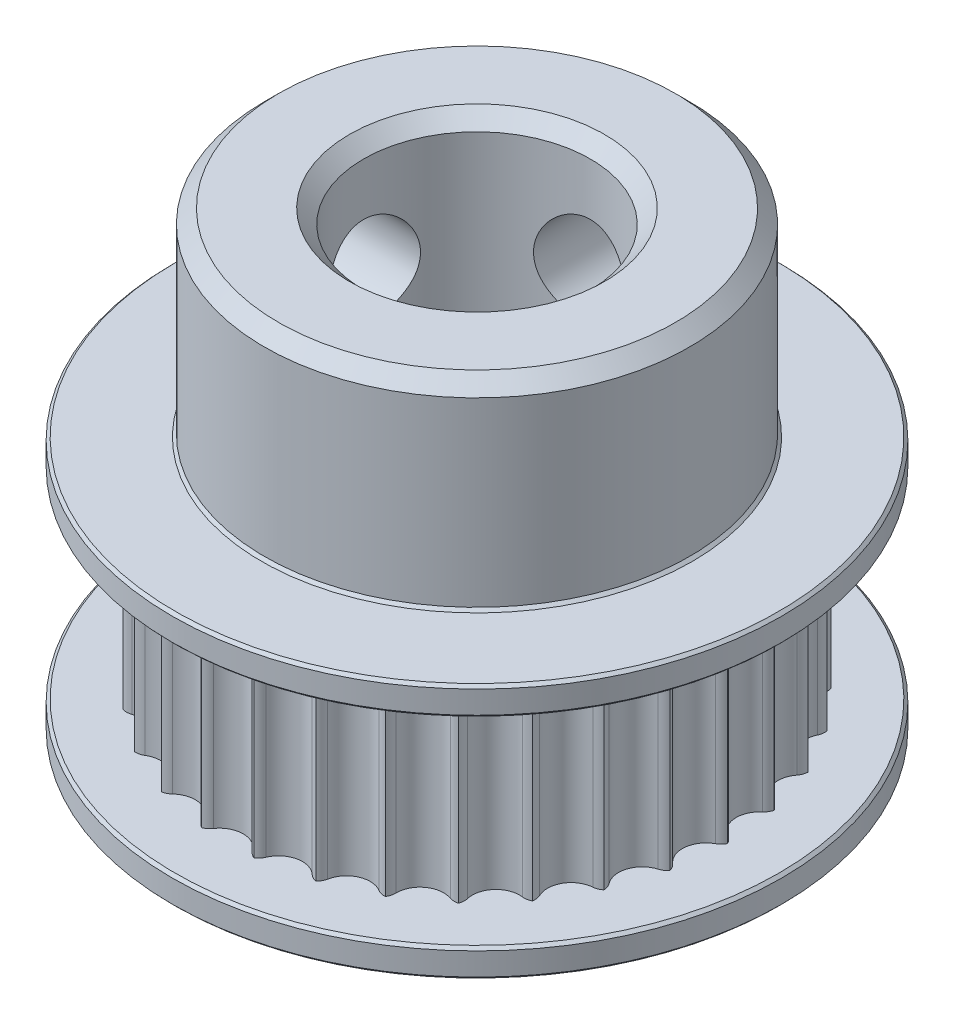
SolidWorks part; units mm, degrees
ref_plane "Front plan" through (0, 0, 0) normal (0, 0, 1) x (1, 0, 0)
ref_plane "Top plan" through (0, 0, 0) normal (0, 1, 0) x (1, 0, 0)
ref_plane "Right plan" through (0, 0, 0) normal (1, 0, 0) x (0, 0, -1)
sketch "Skica2" plane through (0, 0, 0) normal (0, 0, 1) x (1, 0, 0)
  line L0 (7.5, 8.5) -> (4, 8.5)
  line L1 (4, 8.5) -> (4, -8.5)
  line L2 (4, -8.5) -> (6.11, -8.5)
  line L3 (0, -8.5) -> (0, 8.5) construction
  line L4 (0, 8.5) -> (4, 8.5)
  line L5 (0, -8.5) -> (4, -8.5)
  line L6 (6.11, -8.5) -> (6.11, -7.5)
  line L7 (10.75, 0.5) -> (9.25, 0.5)
  line L8 (9.25, 0.5) -> (9.25, -6.5)
  line L9 (10.75, 0.5) -> (10.75, 1.5)
  line L12 (10.75, -7.5) -> (6.11, -7.5)
  line L13 (10.75, 1.5) -> (7.5, 1.5)
  line L14 (10.75, -7.5) -> (10.75, -6.5)
  line L15 (9.25, -6.5) -> (10.75, -6.5)
  line L16 (7.5, 1.5) -> (7.5, 8.5)
  point P2 (9.25, 0.5)
  point P6 (8.43, -7.5)
  point P7 (0, 0)
  point P17 (7.2212, 1.2408)
  dimension "D3" = 18.5
  dimension "D1" = 8
  dimension "D2" = 1
  dimension "D4" = 1
  dimension "D6" = 21.5
  dimension "D7" = 15
  dimension "D8" = 17
  dimension "D9" = 7
revolve "Revolute" add sketch "Skica2" angle 360 about L3 region at (6.4347, -0.5872, 0)
sketch "Sketch2" plane through (0, 0.5, 0) normal (0, -1, 0) x (1, 0, 0)
  line L0 (0, 0) -> (0, 9.0829) construction
  line L1 (0, 0) -> (3.0348, 8.4729) construction
  line L3 (0, 0) -> (-1.6132, 8.7491) construction
  circle A1 centre (0, 0) radius 8.2469 construction
  circle A2 centre (0, 0) radius 8.6357 construction
  arc A3 (-0.6881, 8.6082) -> (0.6881, 8.6082) centre (0, 9.0829) ccw
  arc A7 (-1.1652, 8.82) -> (-1.6132, 8.7491) centre (0, 0) ccw
  arc A8 (0, 10.1685) -> (1.6132, 8.7491) centre (0.3953, 8.9913) cw
  circle A9 centre (0, 0) radius 9 construction
  arc A10 (1.1652, 8.82) -> (1.6132, 8.7491) centre (0, 0) cw
  arc A11 (1.1652, 8.82) -> (0.6881, 8.6082) centre (1.0997, 8.3243) ccw
  arc A12 (0, 10.1685) -> (-1.6132, 8.7491) centre (-0.3953, 8.9913) ccw
  arc A13 (-1.1652, 8.82) -> (-0.6881, 8.6082) centre (-1.0997, 8.3243) cw
  point P0 (-1.0997, 8.3243)
  point P5 (0, 6.1378)
  point P8 (0, 0)
  circle M8 centre (0, 0) radius 9.25
  dimension "D2" = 1
  dimension "D3" = 1.2417
  dimension "D4" = 0.836
  dimension "D6" = 18
extrude "Cut-Extrude1" cut sketch "Sketch2" along normal up to surface (7 mm away) contours A8 M8 | A11 A3 M8 region at (0, 0.5, 8.8612) region at (0, 0.5, 9.6545) up to face at (10.75, -6.5, 0)
pattern_circular "CirPattern1" count 30 over 360 about axis through (0, -8.5, 0) along (0, -1, 0) of "Cut-Extrude1" reverse direction yes
sketch "Sketch3" plane through (0, 0, 0) normal (1, 0, 0) x (0, 0, -1)
  line L0 (0, 8.5) -> (0, 0.5) construction
  line L1 (4, 8.5) -> (-4, 8.5) construction
  circle A0 centre (0, 4.5) radius 1.65
  point P8 (0, 0)
  dimension "D1" = 3.3
extrude "Cut-Extrude2" cut sketch "Sketch3" against normal up to next
sketch "Sketch4" plane through (0, 0, 0) normal (0, 0, 1) x (1, 0, 0)
  line L0 (0, 8.5) -> (0, 0.5) construction
  line L1 (10.75, 8.5) -> (-10.75, 8.5) construction
  line L2 (-0.6881, 0.5) -> (0.6881, 0.5) construction
  circle A0 centre (0, 4.5) radius 1.65
  dimension "D1" = 3.3
extrude "Cut-Extrude3" cut sketch "Sketch4" against normal up to next
chamfer "Chamfer1" distance 1 angle 45 1 edges at (6.11, -7.5, 0)
chamfer "Chamfer2" distance 0.5 angle 45 2 edges at (4, 8.5, 0) (7.5, 8.5, 0)
chamfer "Chamfer3" distance 0.1 angle 45 5 edges at (10.75, -7.5, 0) (10.75, -6.5, 0) (10.75, 0.5, 0) (10.75, 1.5, 0) (7.5, 1.5, 0)
equation "\"`\"=2"
